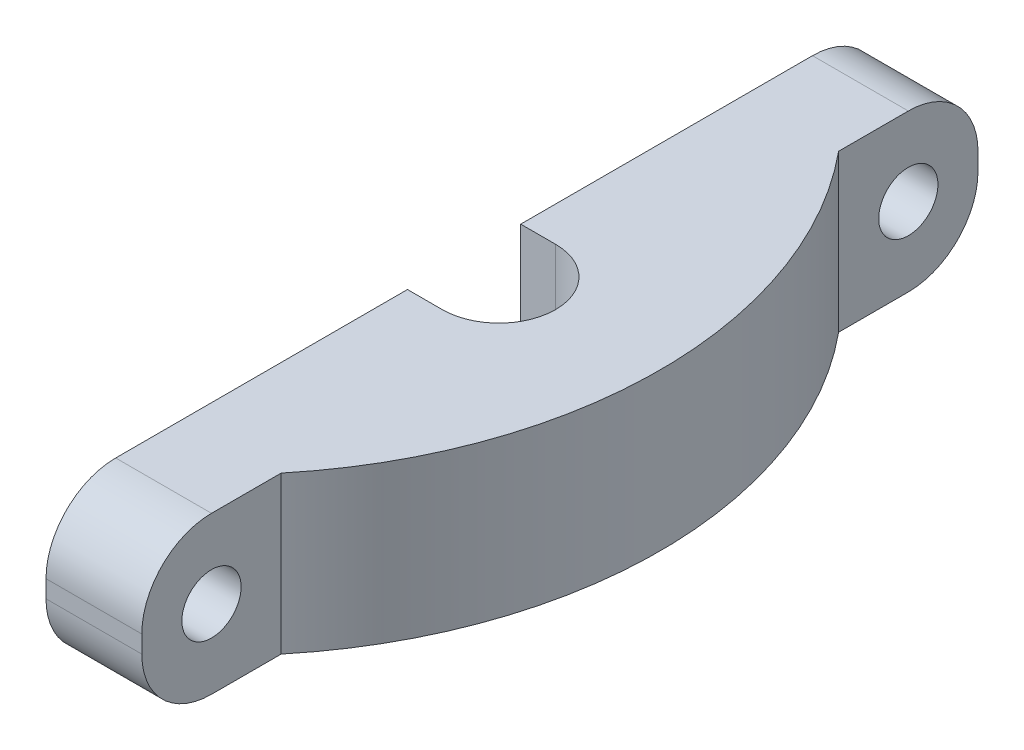
SolidWorks part; units mm, degrees
ref_plane "Front Plane" through (0, 0, 0) normal (0, 0, 1) x (1, 0, 0)
ref_plane "Top Plane" through (0, 0, 0) normal (0, 1, 0) x (1, 0, 0)
ref_plane "Right Plane" through (0, 0, 0) normal (1, 0, 0) x (0, 0, -1)
sketch "Sketch1" plane through (0, 0, 0) normal (1, 0, 0) x (0, 0, -1)
  line L0 (-24, 0) -> (24, 0) construction
  line L3 (-24, 0.5) -> (-24, -0.5)
  line L4 (24, 0.5) -> (24, -0.5)
  line L5 (-20, -4.5) -> (20, -4.5)
  line L6 (20, 4.5) -> (-20, 4.5)
  arc A2 (-24, 0.5) -> (-20, 4.5) centre (-20, 0.5) cw
  arc A3 (-24, -0.5) -> (-20, -4.5) centre (-20, -0.5) ccw
  arc A4 (24, -0.5) -> (20, -4.5) centre (20, -0.5) cw
  arc A5 (24, 0.5) -> (20, 4.5) centre (20, 0.5) ccw
  point P4 (0, 0)
  point P7 (-24, 0)
  point P12 (24, 0)
  point P18 (24, -4.5)
  point P21 (24, 4.5)
  dimension "D3" = 4
  dimension "D1" = 48
  dimension "D2" = 9
extrude "Boss-Extrude1" add sketch "Sketch1" along normal blind 11.25
sketch "Sketch2" plane through (0, -4.5, 0) normal (0, -1, 0) x (-1, 0, 0)
  line L0 (-2, -3.25) -> (0, -3.25)
  line L1 (0, -20) -> (0, 20) construction
  line L2 (-2, 3.25) -> (0, 3.25)
  line L3 (0, -3.25) -> (0, 3.25)
  arc A0 (-2, 3.25) -> (-2, -3.25) centre (-2, 0) ccw
  dimension "D1" = 6.5
  dimension "D2" = 2
extrude "Cut-Extrude1" cut sketch "Sketch2" against normal through all
sketch "Sketch3" plane through (11.25, 0, 0) normal (1, 0, 0) x (0, 0, -1)
  line L0 (-24, 0) -> (24, 0) construction
  line L1 (-24, 0.5) -> (-24, -0.5) construction
  line L2 (24, -0.5) -> (24, 0.5) construction
hole_wizard "M3 Clearance Hole1" positions "Sketch4" profile "Sketch6" hole size "M3" standard "ISO" end condition through all
sketch "Sketch4" plane through (11.25, 0, 0) normal (1, 0, 0) x (0, 0, -1)
  line L0 (-24, 0) -> (24, 0) construction
  line L1 (24, -0.5) -> (24, 0.5) construction
  line L2 (-24, 0.5) -> (-24, -0.5) construction
  point P0 (-20, 0)
  point P4 (20, 0)
  dimension "D1" = 4
  dimension "D2" = 4
sketch "Sketch6" plane through (11.25, 0, 20) normal (0, 1, 0) x (0, 0, -1)
  line L0 (0, 0) -> (0, 11.25)
  line L1 (0, 11.25) -> (1.7, 11.25)
  line L2 (1.7, 11.25) -> (1.7, 0)
  line L5 (1.7, 0) -> (0, 0)
  line L11 (0, -6.35) -> (0, 107.95) construction
  dimension "Thru Hole Dia." = 3.4
  dimension "Thru Hole Depth" = 11.25
sketch "Sketch7" plane through (0, -4.5, 0) normal (0, -1, 0) x (-1, 0, 0)
  line L0 (-5.5, -24) -> (-5.5, -16)
  line L1 (-11.25, -24) -> (0, -24) construction
  line L2 (-5.5, 24) -> (-5.5, 16)
  line L3 (-11.25, 24) -> (0, 24) construction
  line L4 (0, -20) -> (0, -3.25) construction
  line L6 (-11.25, -24) -> (-11.25, 24) construction
  line L7 (-5.5, -24) -> (-11.25, -24)
  line L8 (-11.25, -24) -> (-11.25, 24)
  line L9 (-11.25, 24) -> (-5.5, 24)
  arc A0 (-5.5, -16) -> (-5.5, 16) centre (13.8859, 0) cw
  point P11 (-11.25, 0)
  point P14 (-11.25, 0)
  line M6 (0, 20) -> (-11.25, 20)
  line M7 (-11.25, 20) -> (-11.25, -20)
  line M8 (-11.25, -20) -> (0, -20)
  dimension "D1" = 5.5
  dimension "D2" = 8
extrude "Cut-Extrude2" cut sketch "Sketch7" against normal through all contours L8 L7 L0 M8 | L0 A0 L8 M8 | A0 L2 M7 M6 | L9 L8 L2 M6 region at (8.375, -4.5, 22) region at (9.0398, -4.5, -14.7026) region at (9.0398, -4.5, 14.7026) region at (8.375, -4.5, -22)
